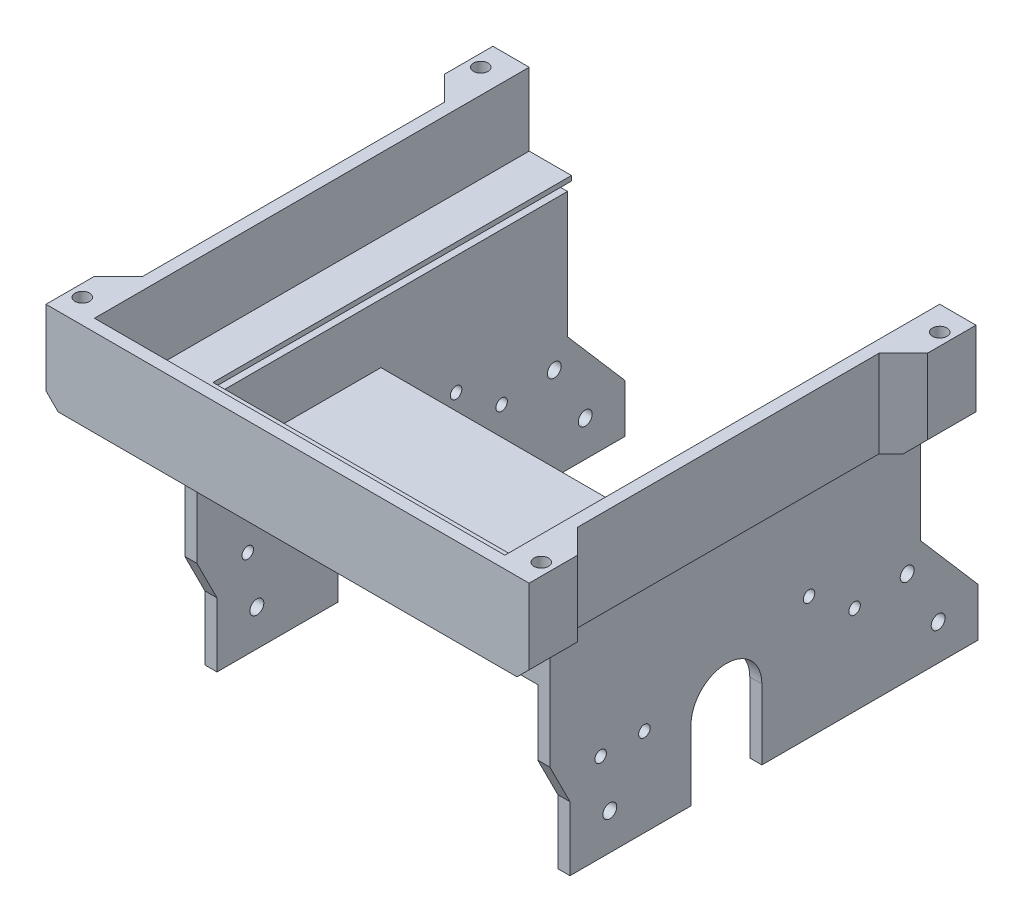
SolidWorks part; units mm, degrees
ref_plane "前视基准面" through (0, 0, 0) normal (0, 0, 1) x (1, 0, 0)
ref_plane "上视基准面" through (0, 0, 0) normal (0, 1, 0) x (1, 0, 0)
ref_plane "右视基准面" through (0, 0, 0) normal (1, 0, 0) x (0, 0, -1)
other "Configuration Table"
sketch "草图1" plane through (0, 0, 0) normal (1, 0, 0) x (0, 0, -1)
  line L0 (33.7, -13.6373) -> (33.7, -5.6373)
  line L1 (-33.7, -13.6373) -> (33.7, -13.6373)
  line L5 (24.2, -13.6373) -> (24.2, 5.3627)
  line L6 (33.7, -5.6373) -> (24.2, -5.6373)
  line L7 (24.2, 5.3627) -> (33.7, -5.6373)
  line L8 (24.2, 5.3627) -> (24.2, 10.3627)
  line L9 (24.2, 10.3627) -> (-37.02, 10.3627)
  line L10 (-33.7, -13.6373) -> (-33.7, -3.0373)
  line L11 (-37.02, 10.3627) -> (-37.02, 3.5627)
  line L12 (-37.02, 3.5627) -> (-33.7, -3.0373)
  line L13 (-33.7, -13.6373) -> (-13.7, -13.6373)
  line L14 (-13.7, -13.6373) -> (-2, -13.6373)
  line L16 (-2, -13.6373) -> (-13.7, -13.6373)
  line L17 (-2, -13.6373) -> (-2, -2.0373)
  line L18 (-2, -2.0373) -> (-13.7, -2.0373)
  line L19 (-13.7, -13.6373) -> (-13.7, -2.0373)
  circle A0 centre (-7.85, -2.0373) radius 5.85
  point P0 (0, 0)
  dimension "D1" = 67.4
  dimension "D2" = 8
  dimension "D3" = 19
  dimension "D4" = 9.5
  dimension "D5" = 5
  dimension "D6" = 61.22
  dimension "D7" = 10.6
  dimension "D8" = 6.8
  dimension "D9" = 20
  dimension "D10" = 11.7
  dimension "D11" = 11.6
extrude "凸台-拉伸1" add sketch "草图1" along normal blind 2 contours A0 L17 L1 L5 L8 L9 L11 L12 L10 L19 | L7 L5 L6 | L0 L6 L5 L1 region at (0, -9.6373, -28.95) region at (0, -1.9707, -27.3667) region at (0, -12.9798, -11.1)
sketch "草图2" plane through (2, 0, 0) normal (1, 0, 0) x (0, 0, -1)
  line L0 (28.27, -7.7273) -> (33.7, -7.7273)
  line L1 (27.12, -8.8773) -> (27.12, -13.6373)
  line L2 (-27.12, -8.7773) -> (-27.12, -13.6373)
  line L3 (-28.27, -7.6273) -> (-33.7, -7.6273)
  line L4 (24.2, 5.3627) -> (24.2, -13.6373)
  line L5 (33.7, 1.7127) -> (23.15, 1.7127)
  line L6 (22, 0.5627) -> (22, -13.6373)
  line L7 (33.7, -5.6373) -> (33.7, 10.3627)
  line L8 (33.7, 10.3627) -> (24.2, 10.3627)
  line L9 (14.26, 1.1127) -> (33.7, 1.1127)
  line L10 (13.31, 0.1627) -> (13.31, -13.6373)
  line L11 (-2, -2.0373) -> (-2, -13.6373)
  line L12 (-2, -13.6373) -> (33.7, -13.6373)
  line L13 (33.7, -13.6373) -> (33.7, -5.6373)
  line L14 (33.7, -5.6373) -> (24.2, 5.3627)
  line L15 (24.2, 5.3627) -> (24.2, 10.3627)
  line L16 (24.2, 10.3627) -> (-37.02, 10.3627)
  line L17 (-37.02, 10.3627) -> (-37.02, 3.5627)
  line L18 (-37.02, 3.5627) -> (-33.7, -3.0373)
  line L19 (-33.7, -3.0373) -> (-33.7, -13.6373)
  line L20 (-33.7, -13.6373) -> (-13.7, -13.6373)
  line L21 (-13.7, -13.6373) -> (-13.7, -2.0373)
  line L22 (-2, -2.0373) -> (-2, -13.6373)
  line L23 (-2, -13.6373) -> (33.7, -13.6373)
  line L24 (33.7, -13.6373) -> (33.7, -5.6373)
  line L25 (33.7, -5.6373) -> (24.2, 5.3627)
  line L26 (24.2, 5.3627) -> (24.2, 10.3627)
  line L27 (24.2, 10.3627) -> (-37.02, 10.3627)
  line L28 (-37.02, 10.3627) -> (-37.02, 3.5627)
  line L29 (-37.02, 3.5627) -> (-33.7, -3.0373)
  line L30 (-33.7, -3.0373) -> (-33.7, -13.6373)
  line L31 (-33.7, -13.6373) -> (-13.7, -13.6373)
  line L32 (-13.7, -13.6373) -> (-13.7, -2.0373)
  line L33 (6.74, 6.5927) -> (24.2, 6.5927)
  line L34 (5.79, 5.6427) -> (5.79, -13.6373)
  line L35 (-37.02, 3.5627) -> (-37.02, -13.6373)
  line L36 (-37.02, -13.6373) -> (-33.7, -13.6373)
  line L37 (-22.36, 0.9127) -> (-37.02, 0.9127)
  line L38 (-21.41, -0.0373) -> (-21.41, -13.6373)
  line L39 (-29.58, 0.9127) -> (-37.02, 0.9127)
  circle A0 centre (27.12, -7.7273) radius 1.15
  arc A1 (-2, -2.0373) -> (-13.7, -2.0373) centre (-7.85, -2.0373) ccw
  arc A2 (-2, -2.0373) -> (-13.7, -2.0373) centre (-7.85, -2.0373) ccw
  circle A3 centre (-27.12, -7.6273) radius 1.15
  circle A6 centre (22, 1.7127) radius 1.15
  circle A7 centre (13.31, 1.1127) radius 0.95
  circle A8 centre (5.79, 6.5927) radius 0.95
  circle A9 centre (-21.41, 0.9127) radius 0.95
  circle A10 centre (-28.63, 0.9127) radius 0.95
  dimension "D2" = 2.3
  dimension "D6" = 2.3
  dimension "D8" = 10.55
  dimension "D11" = 1.9
  dimension "D9" = 2.3
  dimension "D14" = 1.9
  dimension "D17" = 1.9
  dimension "D20" = 1.9
  dimension "D3" = 4.76
  dimension "D4" = 5.43
  dimension "D5" = 4.86
  dimension "D7" = 5.43
  dimension "D10" = 14.2
  dimension "D12" = 19.44
  dimension "D13" = 13.8
  dimension "D15" = 19.28
  dimension "D16" = 17.46
  dimension "D18" = 14.66
  dimension "D19" = 13.6
  dimension "D21" = 7.44
  dimension "D1" = 0
extrude "切除-拉伸1" cut sketch "草图2" against normal through all contours L37 A10 | L37 A10 | A9 | A3 | A8 | A7 | A6 L9 | L9 A6 | A0 L23 region at (2, -7.7273, -27.12) region at (2, 0.8874, -22) region at (2, 1.8983, -22) region at (2, 1.1127, -13.31) region at (2, 6.5927, -5.79) region at (2, 1.3159, 28.63) region at (2, 0.5095, 28.63) region at (2, -7.6273, 27.12) region at (2, 0.9127, 21.41)
sketch "草图3" plane through (0, 10.3627, 0) normal (0, 1, 0) x (1, 0, 0)
  line L4 (0, 24.2) -> (0, -37.02)
  line L5 (0, -37.02) -> (2, -37.02)
  line L6 (2, -37.02) -> (2, 24.2)
  line L7 (2, 24.2) -> (0, 24.2)
  line L8 (0, 24.2) -> (0, -37.02)
  line L9 (0, -37.02) -> (2, -37.02)
  line L10 (2, -37.02) -> (2, 24.2)
  line L11 (2, 24.2) -> (0, 24.2)
  dimension "D1" = 0
extrude "凸台-拉伸2" add sketch "草图3" along normal blind 6
sketch "草图4" plane through (0, 0, 0) normal (-1, 0, 0) x (0, 0, 1)
  line L1 (-24.2, 16.3627) -> (37.02, 16.3627)
  line L2 (-24.2, 16.3627) -> (-24.2, 14.3627)
  line L3 (-24.2, 14.3627) -> (37.02, 14.3627)
  line L4 (37.02, 16.3627) -> (37.02, 14.3627)
  line L11 (13.7, -2.0373) -> (13.7, -13.6373)
  line L12 (13.7, -13.6373) -> (33.7, -13.6373)
  line L13 (33.7, -13.6373) -> (33.7, -3.0373)
  line L14 (33.7, -3.0373) -> (37.02, 3.5627)
  line L15 (37.02, 3.5627) -> (37.02, 16.3627)
  line L16 (37.02, 16.3627) -> (-24.2, 16.3627)
  line L17 (-24.2, 16.3627) -> (-24.2, 5.3627)
  line L18 (-24.2, 5.3627) -> (-33.7, -5.6373)
  line L19 (-33.7, -5.6373) -> (-33.7, -13.6373)
  line L20 (-33.7, -13.6373) -> (2, -13.6373)
  line L21 (2, -13.6373) -> (2, -2.0373)
  line L22 (13.7, -2.0373) -> (13.7, -13.6373)
  line L23 (13.7, -13.6373) -> (33.7, -13.6373)
  line L24 (33.7, -13.6373) -> (33.7, -3.0373)
  line L25 (33.7, -3.0373) -> (37.02, 3.5627)
  line L26 (37.02, 3.5627) -> (37.02, 16.3627)
  line L27 (37.02, 16.3627) -> (-24.2, 16.3627)
  line L28 (-24.2, 16.3627) -> (-24.2, 5.3627)
  line L29 (-24.2, 5.3627) -> (-33.7, -5.6373)
  line L30 (-33.7, -5.6373) -> (-33.7, -13.6373)
  line L31 (-33.7, -13.6373) -> (2, -13.6373)
  line L32 (2, -13.6373) -> (2, -2.0373)
  arc A1 (13.7, -2.0373) -> (2, -2.0373) centre (7.85, -2.0373) ccw
  arc A2 (13.7, -2.0373) -> (2, -2.0373) centre (7.85, -2.0373) ccw
  line M25 (37.02, 3.5627) -> (37.02, 16.3627)
  line M26 (37.02, 16.3627) -> (-24.2, 16.3627)
  line M27 (-24.2, 16.3627) -> (-24.2, 5.3627)
  dimension "D2" = 2
  dimension "D1" = 0
extrude "凸台-拉伸3" add sketch "草图4" along normal blind 58.3 contours L3 M27 M25 M26 region at (0, 15.3627, 6.41)
sketch "草图5" plane through (-58.3, 0, 0) normal (-1, 0, 0) x (0, 0, 1)
  line L11 (37.02, 14.3627) -> (-24.2, 14.3627)
  line L12 (-24.2, 14.3627) -> (-24.2, 5.3627)
  line L13 (-24.2, 5.3627) -> (-33.7, -5.6373)
  line L14 (-33.7, -5.6373) -> (-33.7, -13.6373)
  line L15 (-33.7, -13.6373) -> (2, -13.6373)
  line L16 (2, -13.6373) -> (2, -2.0373)
  line L17 (13.7, -2.0373) -> (13.7, -13.6373)
  line L18 (13.7, -13.6373) -> (33.7, -13.6373)
  line L19 (33.7, -13.6373) -> (33.7, -3.0373)
  line L20 (33.7, -3.0373) -> (37.02, 3.5627)
  line L21 (37.02, 3.5627) -> (37.02, 14.3627)
  line L22 (37.02, 14.3627) -> (-24.2, 14.3627)
  line L23 (-24.2, 14.3627) -> (-24.2, 5.3627)
  line L24 (-24.2, 5.3627) -> (-33.7, -5.6373)
  line L25 (-33.7, -5.6373) -> (-33.7, -13.6373)
  line L26 (-33.7, -13.6373) -> (2, -13.6373)
  line L27 (2, -13.6373) -> (2, -2.0373)
  line L28 (13.7, -2.0373) -> (13.7, -13.6373)
  line L29 (13.7, -13.6373) -> (33.7, -13.6373)
  line L30 (33.7, -13.6373) -> (33.7, -3.0373)
  line L31 (33.7, -3.0373) -> (37.02, 3.5627)
  line L32 (37.02, 3.5627) -> (37.02, 14.3627)
  circle A0 centre (-13.31, 1.1127) radius 0.95 construction
  arc A1 (13.7, -2.0373) -> (2, -2.0373) centre (7.85, -2.0373) ccw
  arc A2 (13.7, -2.0373) -> (2, -2.0373) centre (7.85, -2.0373) ccw
  circle A3 centre (-13.31, 1.1127) radius 0.95
  circle A4 centre (-22, 1.7127) radius 1.15 construction
  circle A5 centre (-22, 1.7127) radius 1.15
  circle A6 centre (-27.12, -7.7273) radius 1.15 construction
  circle A7 centre (-27.12, -7.7273) radius 1.15
  circle A8 centre (-5.79, 6.5927) radius 0.95 construction
  circle A9 centre (-5.79, 6.5927) radius 0.95
  circle A10 centre (21.41, 0.9127) radius 0.95 construction
  circle A11 centre (21.41, 0.9127) radius 0.95
  circle A12 centre (28.63, 0.9127) radius 0.95 construction
  circle A13 centre (28.63, 0.9127) radius 0.95
  circle A14 centre (27.12, -7.6273) radius 1.15 construction
  circle A15 centre (27.12, -7.6273) radius 1.15
  dimension "D1" = 0
extrude "凸台-拉伸4" add sketch "草图5" against normal blind 2
sketch "草图7" plane through (0, 0, 37.02) normal (0, 0, 1) x (1, 0, 0)
  line L0 (-28.15, 14.3627) -> (-28.15, 8.4109) construction
  line L1 (-58.3, 16.3627) -> (-56.3, 16.3627)
  line L2 (-58.3, 16.3627) -> (-58.3, 26.3627)
  line L3 (-58.3, 26.3627) -> (-56.3, 26.3627)
  line L4 (-56.3, 16.3627) -> (-56.3, 26.3627)
  line L5 (-56.3, 26.3627) -> (0, 26.3627)
  line L6 (2, 16.3627) -> (0, 16.3627)
  line L7 (2, 16.3627) -> (2, 26.3627)
  line L8 (2, 16.3627) -> (-58.3, 16.3627)
  line L9 (-58.3, 16.3627) -> (-58.3, 3.5627)
  line L10 (-58.3, 3.5627) -> (-56.3, 3.5627)
  line L11 (-56.3, 3.5627) -> (-56.3, 14.3627)
  line L12 (-56.3, 14.3627) -> (0, 14.3627)
  line L13 (0, 14.3627) -> (0, 3.5627)
  line L14 (0, 3.5627) -> (2, 3.5627)
  line L15 (2, 3.5627) -> (2, 16.3627)
  line L16 (2, 16.3627) -> (-58.3, 16.3627)
  line L17 (-58.3, 16.3627) -> (-58.3, 3.5627)
  line L18 (-58.3, 3.5627) -> (-56.3, 3.5627)
  line L19 (-56.3, 3.5627) -> (-56.3, 14.3627)
  line L20 (-56.3, 14.3627) -> (0, 14.3627)
  line L21 (0, 14.3627) -> (0, 3.5627)
  line L22 (0, 3.5627) -> (2, 3.5627)
  line L23 (2, 3.5627) -> (2, 16.3627)
  line L24 (2, 26.3627) -> (0, 26.3627)
  line L25 (0, 16.3627) -> (0, 26.3627)
  line L26 (-58.15, 26.3627) -> (1.85, 26.3627)
  line L27 (-58.15, 28.7627) -> (-55.65, 28.7627)
  line L28 (-58.15, 26.3627) -> (1.85, 26.3627)
  line L29 (-58.15, 26.3627) -> (-58.15, 27.9627)
  line L30 (-58.15, 27.9627) -> (1.85, 27.9627)
  line L31 (1.85, 26.3627) -> (1.85, 27.9627)
  line L32 (-58.15, 28.7627) -> (-55.65, 28.7627)
  line L33 (-55.65, 28.7627) -> (-55.65, 27.9627)
  line L34 (-60.15, 26.3627) -> (-58.3, 21.3627)
  line L35 (-58.15, 28.7627) -> (-60.15, 28.7627)
  line L36 (-58.15, 28.7627) -> (-58.15, 26.3627)
  line L37 (-58.15, 26.3627) -> (-60.15, 26.3627)
  line L38 (-60.15, 28.7627) -> (-60.15, 26.3627)
  line L39 (-58.15, 28.7627) -> (1.85, 28.7627) construction
  line L40 (3.85, 26.3627) -> (2, 21.3627)
  line L41 (-0.65, 28.7627) -> (-0.65, 27.9627)
  line L42 (1.85, 26.3627) -> (3.85, 26.3627)
  line L43 (3.85, 28.7627) -> (3.85, 26.3627)
  line L44 (1.85, 28.7627) -> (3.85, 28.7627)
  line L45 (1.85, 28.7627) -> (1.85, 26.3627)
  line L46 (1.85, 28.7627) -> (-0.65, 28.7627)
  point P19 (-28.15, 26.3627)
  dimension "D2" = 10
  dimension "D3" = 60
  dimension "D4" = 1.6
  dimension "D6" = 2.5
  dimension "D7" = 2
  dimension "D1" = 0
  dimension "D5" = 0.8
extrude "凸台-拉伸5" add sketch "草图7" against normal up to surface (61.22 mm away) contours L35 L38 L37 L3 L29 L36 | L27 L36 L30 L33 | L2 L37 L34 | L45 L46 L41 L30 | L44 L45 L31 L24 L42 L43 | L42 L7 L40 | L2 L1 L4 L3 | L7 L6 L25 L24 region at (-58.9167, 24.696, 37.02) region at (-59.15, 27.5627, 37.02) region at (-56.9, 28.3627, 37.02) region at (2.85, 27.5627, 37.02) region at (2.6167, 24.696, 37.02) region at (0.6, 28.3627, 37.02) up to face at (-28.15, 10.3627, -24.2)
sketch "草图8" plane through (0, 0, 37.02) normal (0, 0, 1) x (1, 0, 0)
  line L0 (-55.65, 28.7627) -> (-0.65, 28.7627)
  line L24 (0, 16.3627) -> (-56.3, 16.3627)
  line L25 (-56.3, 16.3627) -> (-56.3, 26.3627)
  line L26 (-56.3, 26.3627) -> (-58.15, 26.3627)
  line L27 (-58.15, 26.3627) -> (-58.15, 27.9627)
  line L28 (-58.15, 27.9627) -> (-55.65, 27.9627)
  line L29 (-55.65, 27.9627) -> (-55.65, 28.7627)
  line L30 (-55.65, 28.7627) -> (-60.15, 28.7627)
  line L31 (-60.15, 28.7627) -> (-60.15, 26.3627)
  line L32 (-60.15, 26.3627) -> (-58.3, 21.3627)
  line L33 (-58.3, 21.3627) -> (-58.3, 3.5627)
  line L34 (-58.3, 3.5627) -> (-56.3, 3.5627)
  line L35 (-56.3, 3.5627) -> (-56.3, 14.3627)
  line L36 (-56.3, 14.3627) -> (0, 14.3627)
  line L37 (0, 14.3627) -> (0, 3.5627)
  line L38 (0, 3.5627) -> (2, 3.5627)
  line L39 (2, 3.5627) -> (2, 21.3627)
  line L40 (2, 21.3627) -> (3.85, 26.3627)
  line L41 (3.85, 26.3627) -> (3.85, 28.7627)
  line L42 (3.85, 28.7627) -> (-0.65, 28.7627)
  line L43 (-0.65, 28.7627) -> (-0.65, 27.9627)
  line L44 (-0.65, 27.9627) -> (1.85, 27.9627)
  line L45 (1.85, 27.9627) -> (1.85, 26.3627)
  line L46 (1.85, 26.3627) -> (0, 26.3627)
  line L47 (0, 26.3627) -> (0, 16.3627)
  line L48 (0, 16.3627) -> (-56.3, 16.3627)
  line L49 (-56.3, 16.3627) -> (-56.3, 26.3627)
  line L50 (-56.3, 26.3627) -> (-58.15, 26.3627)
  line L51 (-58.15, 26.3627) -> (-58.15, 27.9627)
  line L52 (-58.15, 27.9627) -> (-55.65, 27.9627)
  line L53 (-55.65, 27.9627) -> (-55.65, 28.7627)
  line L54 (-55.65, 28.7627) -> (-60.15, 28.7627)
  line L55 (-60.15, 28.7627) -> (-60.15, 26.3627)
  line L56 (-60.15, 26.3627) -> (-58.3, 21.3627)
  line L57 (-58.3, 21.3627) -> (-58.3, 3.5627)
  line L58 (-58.3, 3.5627) -> (-56.3, 3.5627)
  line L59 (-56.3, 3.5627) -> (-56.3, 14.3627)
  line L60 (-56.3, 14.3627) -> (0, 14.3627)
  line L61 (0, 14.3627) -> (0, 3.5627)
  line L62 (0, 3.5627) -> (2, 3.5627)
  line L63 (2, 3.5627) -> (2, 21.3627)
  line L64 (2, 21.3627) -> (3.85, 26.3627)
  line L65 (3.85, 26.3627) -> (3.85, 28.7627)
  line L66 (3.85, 28.7627) -> (-0.65, 28.7627)
  line L67 (-0.65, 28.7627) -> (-0.65, 27.9627)
  line L68 (-0.65, 27.9627) -> (1.85, 27.9627)
  line L69 (1.85, 27.9627) -> (1.85, 26.3627)
  line L70 (1.85, 26.3627) -> (0, 26.3627)
  line L71 (0, 26.3627) -> (0, 16.3627)
  line M25 (0, 16.3627) -> (-56.3, 16.3627)
  line M26 (-56.3, 16.3627) -> (-56.3, 26.3627)
  line M27 (-56.3, 26.3627) -> (-58.15, 26.3627)
  line M28 (-58.15, 26.3627) -> (-58.15, 27.9627)
  line M29 (-58.15, 27.9627) -> (-55.65, 27.9627)
  line M30 (-55.65, 27.9627) -> (-55.65, 28.7627)
  line M31 (-55.65, 28.7627) -> (-60.15, 28.7627)
  line M32 (-60.15, 28.7627) -> (-60.15, 26.3627)
  line M33 (-60.15, 26.3627) -> (-58.3, 21.3627)
  line M34 (-58.3, 21.3627) -> (-58.3, 3.5627)
  line M35 (-58.3, 3.5627) -> (-56.3, 3.5627)
  line M36 (-56.3, 3.5627) -> (-56.3, 14.3627)
  line M37 (-56.3, 14.3627) -> (0, 14.3627)
  line M38 (0, 14.3627) -> (0, 3.5627)
  line M39 (0, 3.5627) -> (2, 3.5627)
  line M40 (2, 3.5627) -> (2, 21.3627)
  line M41 (2, 21.3627) -> (3.85, 26.3627)
  line M42 (3.85, 26.3627) -> (3.85, 28.7627)
  line M43 (3.85, 28.7627) -> (-0.65, 28.7627)
  line M44 (-0.65, 28.7627) -> (-0.65, 27.9627)
  line M45 (-0.65, 27.9627) -> (1.85, 27.9627)
  line M46 (1.85, 27.9627) -> (1.85, 26.3627)
  line M47 (1.85, 26.3627) -> (0, 26.3627)
  line M48 (0, 26.3627) -> (0, 16.3627)
  dimension "D1" = 0
extrude "凸台-拉伸6" add sketch "草图8" against normal blind 2 contours L0 M30 M29 M28 M27 M26 M25 M48 M47 M46 M45 M44 | M48 M25 M26 M27 M28 M29 M30 M31 M32 M33 M34 M35 M36 M37 M38 M39 M40 M41 M42 M43 M44 M45 M46 M47 region at (-28.15, 22.5928, 37.02) region at (-28.15, 16.3288, 37.02)
sketch "草图10" plane through (0, 26.3627, 0) normal (0, 1, 0) x (1, 0, 0)
  line L4 (0, 24.2) -> (0, -35.02)
  line L5 (0, -35.02) -> (1.85, -35.02)
  line L6 (1.85, -35.02) -> (1.85, 24.2)
  line L7 (1.85, 24.2) -> (0, 24.2)
  line L8 (0, 24.2) -> (0, -35.02)
  line L9 (0, -35.02) -> (1.85, -35.02)
  line L10 (1.85, -35.02) -> (1.85, 24.2)
  line L11 (1.85, 24.2) -> (0, 24.2)
  line L12 (-58.15, -35.02) -> (-56.3, -35.02)
  line L13 (-56.3, -35.02) -> (-56.3, 24.2)
  line L14 (-56.3, 24.2) -> (-58.15, 24.2)
  line L15 (-58.15, 24.2) -> (-58.15, -35.02)
  line L16 (-58.15, -35.02) -> (-56.3, -35.02)
  line L17 (-56.3, -35.02) -> (-56.3, 24.2)
  line L18 (-56.3, 24.2) -> (-58.15, 24.2)
  line L19 (-58.15, 24.2) -> (-58.15, -35.02)
  dimension "D1" = 0
  dimension "D2" = 0
extrude "切除-拉伸2" cut sketch "草图10" against normal blind 0.2
sketch "草图11" plane through (0, 0, -24.2) normal (0, 0, -1) x (-1, 0, 0)
  line L1 (-1.85, 26.1627) -> (-1.97, 26.1627)
  line L2 (-1.85, 26.1627) -> (-1.85, 27.9627)
  line L3 (-1.85, 27.9627) -> (-1.97, 27.9627)
  line L4 (-1.97, 26.1627) -> (-1.97, 27.9627)
  line L5 (58.15, 27.9627) -> (58.27, 27.9627)
  line L6 (58.15, 27.9627) -> (58.15, 26.1627)
  line L7 (58.15, 26.1627) -> (58.27, 26.1627)
  line L8 (58.27, 27.9627) -> (58.27, 26.1627)
  line L24 (0, 26.1627) -> (-1.85, 26.1627)
  line L25 (-1.85, 26.1627) -> (-1.85, 27.9627)
  line L26 (-1.85, 27.9627) -> (0.65, 27.9627)
  line L27 (0.65, 27.9627) -> (0.65, 28.7627)
  line L28 (0.65, 28.7627) -> (-3.85, 28.7627)
  line L29 (-3.85, 28.7627) -> (-3.85, 26.3627)
  line L30 (-3.85, 26.3627) -> (-2, 21.3627)
  line L31 (-2, 21.3627) -> (-2, 5.3627)
  line L32 (-2, 5.3627) -> (0, 5.3627)
  line L33 (0, 5.3627) -> (0, 14.3627)
  line L34 (0, 14.3627) -> (56.3, 14.3627)
  line L35 (56.3, 14.3627) -> (56.3, 5.3627)
  line L36 (56.3, 5.3627) -> (58.3, 5.3627)
  line L37 (58.3, 5.3627) -> (58.3, 21.3627)
  line L38 (58.3, 21.3627) -> (60.15, 26.3627)
  line L39 (60.15, 26.3627) -> (60.15, 28.7627)
  line L40 (60.15, 28.7627) -> (55.65, 28.7627)
  line L41 (55.65, 28.7627) -> (55.65, 27.9627)
  line L42 (55.65, 27.9627) -> (58.15, 27.9627)
  line L43 (58.15, 27.9627) -> (58.15, 26.1627)
  line L44 (58.15, 26.1627) -> (56.3, 26.1627)
  line L45 (56.3, 26.1627) -> (56.3, 16.3627)
  line L46 (56.3, 16.3627) -> (0, 16.3627)
  line L47 (0, 16.3627) -> (0, 26.1627)
  line L48 (0, 26.1627) -> (-1.85, 26.1627)
  line L49 (-1.85, 26.1627) -> (-1.85, 27.9627)
  line L50 (-1.85, 27.9627) -> (0.65, 27.9627)
  line L51 (0.65, 27.9627) -> (0.65, 28.7627)
  line L52 (0.65, 28.7627) -> (-3.85, 28.7627)
  line L53 (-3.85, 28.7627) -> (-3.85, 26.3627)
  line L54 (-3.85, 26.3627) -> (-2, 21.3627)
  line L55 (-2, 21.3627) -> (-2, 5.3627)
  line L56 (-2, 5.3627) -> (0, 5.3627)
  line L57 (0, 5.3627) -> (0, 14.3627)
  line L58 (0, 14.3627) -> (56.3, 14.3627)
  line L59 (56.3, 14.3627) -> (56.3, 5.3627)
  line L60 (56.3, 5.3627) -> (58.3, 5.3627)
  line L61 (58.3, 5.3627) -> (58.3, 21.3627)
  line L62 (58.3, 21.3627) -> (60.15, 26.3627)
  line L63 (60.15, 26.3627) -> (60.15, 28.7627)
  line L64 (60.15, 28.7627) -> (55.65, 28.7627)
  line L65 (55.65, 28.7627) -> (55.65, 27.9627)
  line L66 (55.65, 27.9627) -> (58.15, 27.9627)
  line L67 (58.15, 27.9627) -> (58.15, 26.1627)
  line L68 (58.15, 26.1627) -> (56.3, 26.1627)
  line L69 (56.3, 26.1627) -> (56.3, 16.3627)
  line L70 (56.3, 16.3627) -> (0, 16.3627)
  line L71 (0, 16.3627) -> (0, 26.1627)
  line M28 (-1.85, 26.1627) -> (-1.85, 27.9627)
  line M46 (58.15, 27.9627) -> (58.15, 26.1627)
  dimension "D2" = 0.12
  dimension "D3" = 0.12
  dimension "D1" = 0
extrude "切除-拉伸4" cut sketch "草图11" against normal up to surface (59.22 mm away) contours L4 L1 L3 M28 | L8 L5 L7 M46 region at (1.91, 27.0627, -24.2) region at (-58.21, 27.0627, -24.2) up to face at (-28.15, 25.5627, 35.02)
sketch "草图12" plane through (0, 0, -24.2) normal (0, 0, -1) x (-1, 0, 0)
  line L1 (0, 16.3627) -> (56.3, 16.3627)
  line L2 (0, 16.3627) -> (0, 14.3627)
  line L3 (0, 14.3627) -> (56.3, 14.3627)
  line L4 (56.3, 16.3627) -> (56.3, 14.3627)
  line L24 (-1.97, 26.1627) -> (-1.97, 27.9627)
  line L25 (-1.97, 27.9627) -> (0.65, 27.9627)
  line L26 (0.65, 27.9627) -> (0.65, 28.7627)
  line L27 (0.65, 28.7627) -> (-3.85, 28.7627)
  line L28 (-3.85, 28.7627) -> (-3.85, 26.3627)
  line L29 (-3.85, 26.3627) -> (-2, 21.3627)
  line L30 (-2, 21.3627) -> (-2, 5.3627)
  line L31 (-2, 5.3627) -> (0, 5.3627)
  line L32 (0, 5.3627) -> (0, 14.3627)
  line L33 (0, 14.3627) -> (56.3, 14.3627)
  line L34 (56.3, 14.3627) -> (56.3, 5.3627)
  line L35 (56.3, 5.3627) -> (58.3, 5.3627)
  line L36 (58.3, 5.3627) -> (58.3, 21.3627)
  line L37 (58.3, 21.3627) -> (60.15, 26.3627)
  line L38 (60.15, 26.3627) -> (60.15, 28.7627)
  line L39 (60.15, 28.7627) -> (55.65, 28.7627)
  line L40 (55.65, 28.7627) -> (55.65, 27.9627)
  line L41 (55.65, 27.9627) -> (58.27, 27.9627)
  line L42 (58.27, 27.9627) -> (58.27, 26.1627)
  line L43 (58.27, 26.1627) -> (56.3, 26.1627)
  line L44 (56.3, 26.1627) -> (56.3, 16.3627)
  line L45 (56.3, 16.3627) -> (0, 16.3627)
  line L46 (0, 16.3627) -> (0, 26.1627)
  line L47 (0, 26.1627) -> (-1.97, 26.1627)
  line L48 (-1.97, 26.1627) -> (-1.97, 27.9627)
  line L49 (-1.97, 27.9627) -> (0.65, 27.9627)
  line L50 (0.65, 27.9627) -> (0.65, 28.7627)
  line L51 (0.65, 28.7627) -> (-3.85, 28.7627)
  line L52 (-3.85, 28.7627) -> (-3.85, 26.3627)
  line L53 (-3.85, 26.3627) -> (-2, 21.3627)
  line L54 (-2, 21.3627) -> (-2, 5.3627)
  line L55 (-2, 5.3627) -> (0, 5.3627)
  line L56 (0, 5.3627) -> (0, 14.3627)
  line L57 (0, 14.3627) -> (56.3, 14.3627)
  line L58 (56.3, 14.3627) -> (56.3, 5.3627)
  line L59 (56.3, 5.3627) -> (58.3, 5.3627)
  line L60 (58.3, 5.3627) -> (58.3, 21.3627)
  line L61 (58.3, 21.3627) -> (60.15, 26.3627)
  line L62 (60.15, 26.3627) -> (60.15, 28.7627)
  line L63 (60.15, 28.7627) -> (55.65, 28.7627)
  line L64 (55.65, 28.7627) -> (55.65, 27.9627)
  line L65 (55.65, 27.9627) -> (58.27, 27.9627)
  line L66 (58.27, 27.9627) -> (58.27, 26.1627)
  line L67 (58.27, 26.1627) -> (56.3, 26.1627)
  line L68 (56.3, 26.1627) -> (56.3, 16.3627)
  line L69 (56.3, 16.3627) -> (0, 16.3627)
  line L70 (0, 16.3627) -> (0, 26.1627)
  line L71 (0, 26.1627) -> (-1.97, 26.1627)
  line M38 (0, 14.3627) -> (56.3, 14.3627)
  line M50 (56.3, 16.3627) -> (0, 16.3627)
  dimension "D1" = 0
extrude "切除-拉伸5" cut sketch "草图12" against normal up to surface (30.82 mm away) contours L4 L2 M50 M38 region at (-28.15, 15.3627, -24.2)
sketch "草图13" plane through (0, 0, 37.02) normal (0, 0, 1) x (1, 0, 0)
  line L0 (-58.3, 21.3627) -> (2, 21.3627)
  line L12 (3.85, 26.3627) -> (3.85, 28.7627)
  line L13 (3.85, 28.7627) -> (-60.15, 28.7627)
  line L14 (-60.15, 28.7627) -> (-60.15, 26.3627)
  line L15 (-60.15, 26.3627) -> (-58.3, 21.3627)
  line L16 (-58.3, 21.3627) -> (-58.3, 3.5627)
  line L17 (-58.3, 3.5627) -> (-56.3, 3.5627)
  line L18 (-56.3, 3.5627) -> (-56.3, 14.3627)
  line L19 (-56.3, 14.3627) -> (0, 14.3627)
  line L20 (0, 14.3627) -> (0, 3.5627)
  line L21 (0, 3.5627) -> (2, 3.5627)
  line L22 (2, 3.5627) -> (2, 21.3627)
  line L23 (2, 21.3627) -> (3.85, 26.3627)
  line L24 (3.85, 26.3627) -> (3.85, 28.7627)
  line L25 (3.85, 28.7627) -> (-60.15, 28.7627)
  line L26 (-60.15, 28.7627) -> (-60.15, 26.3627)
  line L27 (-60.15, 26.3627) -> (-58.3, 21.3627)
  line L28 (-58.3, 21.3627) -> (-58.3, 3.5627)
  line L29 (-58.3, 3.5627) -> (-56.3, 3.5627)
  line L30 (-56.3, 3.5627) -> (-56.3, 14.3627)
  line L31 (-56.3, 14.3627) -> (0, 14.3627)
  line L32 (0, 14.3627) -> (0, 3.5627)
  line L33 (0, 3.5627) -> (2, 3.5627)
  line L34 (2, 3.5627) -> (2, 21.3627)
  line L35 (2, 21.3627) -> (3.85, 26.3627)
  line M14 (3.85, 26.3627) -> (3.85, 28.7627)
  line M15 (3.85, 28.7627) -> (-60.15, 28.7627)
  line M16 (-60.15, 28.7627) -> (-60.15, 26.3627)
  line M17 (-60.15, 26.3627) -> (-58.3, 21.3627)
  line M25 (2, 21.3627) -> (3.85, 26.3627)
  dimension "D1" = 0
extrude "凸台-拉伸7" add sketch "草图13" along normal up to surface (10.6 mm away) contours L0 M17 M25 M14 M15 M16 region at (-28.15, 25.1032, 37.02)
sketch "草图14" plane through (3.85, 0, 0) normal (1, 0, 0) x (0, 0, -1)
  line L4 (24.2, 28.7627) -> (-47.62, 28.7627)
  line L5 (-47.62, 28.7627) -> (-47.62, 26.3627)
  line L6 (-47.62, 26.3627) -> (24.2, 26.3627)
  line L7 (24.2, 26.3627) -> (24.2, 28.7627)
  line L8 (24.2, 28.7627) -> (-47.62, 28.7627)
  line L9 (-47.62, 28.7627) -> (-47.62, 26.3627)
  line L10 (-47.62, 26.3627) -> (24.2, 26.3627)
  line L11 (24.2, 26.3627) -> (24.2, 28.7627)
  dimension "D1" = 0
extrude "凸台-拉伸8" add sketch "草图14" along normal up to surface (1.32 mm away)
sketch "草图15" plane through (-60.15, 0, 0) normal (-1, 0, 0) x (0, 0, 1)
  line L4 (-24.2, 26.3627) -> (47.62, 26.3627)
  line L5 (47.62, 26.3627) -> (47.62, 28.7627)
  line L6 (47.62, 28.7627) -> (-24.2, 28.7627)
  line L7 (-24.2, 28.7627) -> (-24.2, 26.3627)
  line L8 (-24.2, 26.3627) -> (47.62, 26.3627)
  line L9 (47.62, 26.3627) -> (47.62, 28.7627)
  line L10 (47.62, 28.7627) -> (-24.2, 28.7627)
  line L11 (-24.2, 28.7627) -> (-24.2, 26.3627)
  dimension "D1" = 0
extrude "凸台-拉伸9" add sketch "草图15" along normal up to surface (2.48 mm away) up to face at (1, -13.6373, -15.85)
sketch "草图16" plane through (0, 0, 47.62) normal (0, 0, 1) x (1, 0, 0)
  line L8 (-58.3, 21.3627) -> (2, 21.3627)
  line L9 (2, 21.3627) -> (3.85, 26.3627)
  line L10 (3.85, 26.3627) -> (5.17, 26.3627)
  line L11 (5.17, 26.3627) -> (5.17, 28.7627)
  line L12 (5.17, 28.7627) -> (-62.63, 28.7627)
  line L13 (-62.63, 28.7627) -> (-62.63, 26.3627)
  line L14 (-62.63, 26.3627) -> (-60.15, 26.3627)
  line L15 (-60.15, 26.3627) -> (-58.3, 21.3627)
  line L16 (-58.3, 21.3627) -> (2, 21.3627)
  line L17 (2, 21.3627) -> (3.85, 26.3627)
  line L18 (3.85, 26.3627) -> (5.17, 26.3627)
  line L19 (5.17, 26.3627) -> (5.17, 28.7627)
  line L20 (5.17, 28.7627) -> (-62.63, 28.7627)
  line L21 (-62.63, 28.7627) -> (-62.63, 26.3627)
  line L22 (-62.63, 26.3627) -> (-60.15, 26.3627)
  line L23 (-60.15, 26.3627) -> (-58.3, 21.3627)
  dimension "D1" = 0
extrude "凸台-拉伸10" add sketch "草图16" along normal blind 2
sketch "草图17" plane through (5.17, 0, 0) normal (1, 0, 0) x (0, 0, -1)
  line L4 (24.2, 28.7627) -> (-49.62, 28.7627)
  line L5 (-49.62, 28.7627) -> (-49.62, 26.3627)
  line L6 (-49.62, 26.3627) -> (24.2, 26.3627)
  line L7 (24.2, 26.3627) -> (24.2, 28.7627)
  line L8 (24.2, 28.7627) -> (-49.62, 28.7627)
  line L9 (-49.62, 28.7627) -> (-49.62, 26.3627)
  line L10 (-49.62, 26.3627) -> (24.2, 26.3627)
  line L11 (24.2, 26.3627) -> (24.2, 28.7627)
  dimension "D1" = 0
extrude "凸台-拉伸11" add sketch "草图17" along normal blind 2
sketch "草图18" plane through (-62.63, 0, 0) normal (-1, 0, 0) x (0, 0, 1)
  line L4 (49.62, 28.7627) -> (-24.2, 28.7627)
  line L5 (-24.2, 28.7627) -> (-24.2, 26.3627)
  line L6 (-24.2, 26.3627) -> (49.62, 26.3627)
  line L7 (49.62, 26.3627) -> (49.62, 28.7627)
  line L8 (49.62, 28.7627) -> (-24.2, 28.7627)
  line L9 (-24.2, 28.7627) -> (-24.2, 26.3627)
  line L10 (-24.2, 26.3627) -> (49.62, 26.3627)
  line L11 (49.62, 26.3627) -> (49.62, 28.7627)
  dimension "D1" = 0
extrude "凸台-拉伸12" add sketch "草图18" along normal blind 2
sketch "草图19" plane through (0, 28.7627, 0) normal (0, 1, 0) x (1, 0, 0)
  line L0 (-62.63, 22.2) -> (-62.63, -47.62)
  line L1 (-62.63, -47.62) -> (5.17, -47.62)
  line L2 (5.17, -47.62) -> (5.17, 22.2)
  line L3 (5.17, 22.2) -> (1.35, 22.2)
  line L4 (1.35, 22.2) -> (1.35, -37.02)
  line L5 (1.35, -37.02) -> (-57.65, -37.02)
  line L6 (-57.65, -37.02) -> (-57.65, 22.2)
  line L7 (-57.65, 22.2) -> (-62.63, 22.2)
  line L8 (-55.65, 24.2) -> (-64.63, 24.2)
  line L9 (-64.63, 24.2) -> (-64.63, -49.62)
  line L10 (-64.63, -49.62) -> (7.17, -49.62)
  line L11 (7.17, -49.62) -> (7.17, 24.2)
  line L12 (7.17, 24.2) -> (-0.65, 24.2)
  line L13 (-0.65, 24.2) -> (-0.65, -35.02)
  line L14 (-0.65, -35.02) -> (-55.65, -35.02)
  line L15 (-55.65, -35.02) -> (-55.65, 24.2)
  line L16 (-55.65, 24.2) -> (-64.63, 24.2)
  line L17 (-64.63, 24.2) -> (-64.63, -49.62)
  line L18 (-64.63, -49.62) -> (7.17, -49.62)
  line L19 (7.17, -49.62) -> (7.17, 24.2)
  line L20 (7.17, 24.2) -> (-0.65, 24.2)
  line L21 (-0.65, 24.2) -> (-0.65, -35.02)
  line L22 (-0.65, -35.02) -> (-55.65, -35.02)
  line L23 (-55.65, -35.02) -> (-55.65, 24.2)
  line L24 (-62.63, 22.2) -> (-62.63, 24.2)
  line L25 (-62.63, 24.2) -> (1.35, 24.2)
  line L26 (1.35, 24.2) -> (1.35, 22.2)
  line L27 (5.17, 22.2) -> (5.17, 24.2)
  line M13 (-64.63, 24.2) -> (-64.63, -49.62)
  line M14 (-64.63, -49.62) -> (7.17, -49.62)
  line M15 (7.17, -49.62) -> (7.17, 24.2)
  line M16 (7.17, 24.2) -> (-0.65, 24.2)
  dimension "D1" = 0
  dimension "D2" = 2
extrude "凸台-拉伸13" add sketch "草图19" along normal blind 12 contours L27 L2 L1 L0 L24 L16 M13 M14 M15 M16 region at (-63.6598, 28.7627, 12.71)
sketch "草图20" plane through (0, 40.7627, 0) normal (0, 1, 0) x (1, 0, 0)
  line L0 (-28.73, -49.62) -> (-28.73, -39.7517)
  line L1 (-64.63, 24.2) -> (-68.63, 24.2)
  line L2 (-64.63, 24.2) -> (-64.63, 16.2)
  line L3 (-64.63, 16.2) -> (-68.63, 16.2)
  line L4 (-68.63, 24.2) -> (-68.63, 16.2)
  line L5 (-64.63, -49.62) -> (-68.63, -49.62)
  line L6 (-64.63, -49.62) -> (-64.63, -41.62)
  line L7 (-64.63, -41.62) -> (-68.63, -41.62)
  line L8 (5.17, 24.2) -> (5.17, -47.62)
  line L9 (5.17, -47.62) -> (-62.63, -47.62)
  line L10 (-62.63, -47.62) -> (-62.63, 24.2)
  line L11 (-62.63, 24.2) -> (-64.63, 24.2)
  line L12 (-64.63, 24.2) -> (-64.63, -49.62)
  line L13 (-64.63, -49.62) -> (7.17, -49.62)
  line L14 (7.17, -49.62) -> (7.17, 24.2)
  line L15 (7.17, 24.2) -> (5.17, 24.2)
  line L16 (5.17, 24.2) -> (5.17, -47.62)
  line L17 (5.17, -47.62) -> (-62.63, -47.62)
  line L18 (-62.63, -47.62) -> (-62.63, 24.2)
  line L19 (-62.63, 24.2) -> (-64.63, 24.2)
  line L20 (-64.63, 24.2) -> (-64.63, -49.62)
  line L21 (-64.63, -49.62) -> (7.17, -49.62)
  line L22 (7.17, -49.62) -> (7.17, 24.2)
  line L23 (7.17, 24.2) -> (5.17, 24.2)
  line L24 (-68.63, -49.62) -> (-68.63, -41.62)
  line L25 (7.17, -41.62) -> (11.17, -41.62)
  line L26 (11.17, -49.62) -> (11.17, -41.62)
  line L27 (7.17, -49.62) -> (11.17, -49.62)
  line L28 (7.17, -49.62) -> (7.17, -41.62)
  line L29 (7.17, 16.2) -> (11.17, 16.2)
  line L30 (11.17, 24.2) -> (11.17, 16.2)
  line L31 (7.17, 24.2) -> (11.17, 24.2)
  line L32 (7.17, 24.2) -> (7.17, 16.2)
  line L33 (-68.63, 24.2) -> (-64.63, 16.2)
  line L34 (-68.63, -41.62) -> (-64.63, -49.62)
  circle A0 centre (-66.63, 20.2) radius 1.2
  circle A1 centre (-66.63, -45.62) radius 1.2
  circle A2 centre (9.17, 20.2) radius 1.2
  circle A3 centre (9.17, -45.62) radius 1.2
  line M22 (-64.63, 24.2) -> (-64.63, -49.62)
  line M24 (7.17, -49.62) -> (7.17, 24.2)
  dimension "D5" = 2.4
  dimension "D6" = 2.4
  dimension "D2" = 4
  dimension "D3" = 8
  dimension "D4" = 8
  dimension "D1" = 0
extrude "凸台-拉伸14" add sketch "草图20" against normal blind 10 contours A0 L33 L1 M22 | A0 L33 L4 L3 | A1 L34 L7 M22 | A1 L34 L24 L5 | L27 L26 L25 A3 M24 | L31 L29 L30 A2 M24 region at (-65.9286, 40.7627, 44.1046) region at (-67.3314, 40.7627, 47.1354) region at (7.2594, 40.7627, 45.62) region at (-65.9286, 40.7627, -21.7154) region at (-67.3314, 40.7627, -18.6846) region at (7.2594, 40.7627, -20.2)
sketch "草图21" plane through (0, 30.7627, 0) normal (0, -1, 0) x (1, 0, 0)
  line L0 (-64.63, 49.62) -> (-68.63, 49.62) construction
  line L1 (-68.63, 49.62) -> (-68.63, 41.62) construction
  line L2 (-68.63, 41.62) -> (-64.63, 41.62) construction
  line L3 (-64.63, 41.62) -> (-64.63, 49.62) construction
  line L4 (-64.63, -16.2) -> (-68.63, -16.2)
  line L5 (-68.63, -16.2) -> (-68.63, -24.2)
  line L6 (-68.63, -24.2) -> (-64.63, -24.2)
  line L7 (-64.63, -24.2) -> (-64.63, -16.2)
  line L8 (-64.63, -16.2) -> (-68.63, -16.2)
  line L9 (-68.63, -16.2) -> (-68.63, -24.2)
  line L10 (-68.63, -24.2) -> (-64.63, -24.2)
  line L11 (-64.63, -24.2) -> (-64.63, -16.2)
  line L12 (7.17, -24.2) -> (11.17, -24.2) construction
  line L13 (11.17, -24.2) -> (11.17, -16.2) construction
  line L14 (11.17, -16.2) -> (7.17, -16.2) construction
  line L15 (7.17, -16.2) -> (7.17, -24.2) construction
  line L16 (7.17, 49.62) -> (7.17, 41.62) construction
  line L17 (7.17, 41.62) -> (11.17, 41.62) construction
  line L18 (11.17, 41.62) -> (11.17, 49.62) construction
  line L19 (11.17, 49.62) -> (7.17, 49.62) construction
  line L20 (-64.63, 49.62) -> (-68.63, 49.62)
  line L21 (-68.63, 49.62) -> (-68.63, 41.62)
  line L22 (-68.63, 41.62) -> (-64.63, 41.62)
  line L23 (-64.63, 41.62) -> (-64.63, 49.62)
  line L24 (7.17, -24.2) -> (11.17, -24.2)
  line L25 (11.17, -24.2) -> (11.17, -16.2)
  line L26 (11.17, -16.2) -> (7.17, -16.2)
  line L27 (7.17, -16.2) -> (7.17, -24.2)
  line L28 (7.17, 49.62) -> (7.17, 41.62)
  line L29 (7.17, 41.62) -> (11.17, 41.62)
  line L30 (11.17, 41.62) -> (11.17, 49.62)
  line L31 (11.17, 49.62) -> (7.17, 49.62)
  dimension "D1" = 0
extrude "凸台-拉伸15" add sketch "草图21" against normal blind 3
sketch "草图22" plane through (0, 30.7627, 0) normal (0, -1, 0) x (1, 0, 0)
  line L4 (-64.63, 49.62) -> (-68.63, 49.62)
  line L5 (-68.63, 49.62) -> (-68.63, 41.62)
  line L6 (-68.63, 41.62) -> (-64.63, 41.62)
  line L7 (-64.63, 41.62) -> (-64.63, 49.62)
  line L8 (-64.63, 49.62) -> (-68.63, 49.62)
  line L9 (-68.63, 49.62) -> (-68.63, 41.62)
  line L10 (-68.63, 41.62) -> (-64.63, 41.62)
  line L11 (-64.63, 41.62) -> (-64.63, 49.62)
  line L12 (-64.63, -16.2) -> (-68.63, -16.2)
  line L13 (-68.63, -16.2) -> (-68.63, -24.2)
  line L14 (-68.63, -24.2) -> (-64.63, -24.2)
  line L15 (-64.63, -24.2) -> (-64.63, -16.2)
  line L16 (-64.63, -16.2) -> (-68.63, -16.2)
  line L17 (-68.63, -16.2) -> (-68.63, -24.2)
  line L18 (-68.63, -24.2) -> (-64.63, -24.2)
  line L19 (-64.63, -24.2) -> (-64.63, -16.2)
  line L20 (7.17, -24.2) -> (11.17, -24.2)
  line L21 (11.17, -24.2) -> (11.17, -16.2)
  line L22 (11.17, -16.2) -> (7.17, -16.2)
  line L23 (7.17, -16.2) -> (7.17, -24.2)
  line L24 (7.17, -24.2) -> (11.17, -24.2)
  line L25 (11.17, -24.2) -> (11.17, -16.2)
  line L26 (11.17, -16.2) -> (7.17, -16.2)
  line L27 (7.17, -16.2) -> (7.17, -24.2)
  line L28 (7.17, 49.62) -> (7.17, 41.62)
  line L29 (7.17, 41.62) -> (11.17, 41.62)
  line L30 (11.17, 41.62) -> (11.17, 49.62)
  line L31 (11.17, 49.62) -> (7.17, 49.62)
  line L32 (7.17, 49.62) -> (7.17, 41.62)
  line L33 (7.17, 41.62) -> (11.17, 41.62)
  line L34 (11.17, 41.62) -> (11.17, 49.62)
  line L35 (11.17, 49.62) -> (7.17, 49.62)
  dimension "D1" = 0
  dimension "D2" = 0
  dimension "D3" = 0
  dimension "D4" = 0
extrude "凸台-拉伸16" add sketch "草图22" along normal up to surface (4.4 mm away) up to face at (-62.39, 26.3627, 12.71)
chamfer "倒角1" distance 4 angle 45 4 edges at (7.17, 33.5627, 41.62) (7.17, 33.5627, -16.2) (-64.63, 33.5627, 41.62) (-64.63, 33.5627, -16.2)
chamfer "倒角2" distance 2 angle 45 4 edges at (11.17, 26.3627, -20.2) (11.17, 26.3627, 45.62) (-68.63, 26.3627, -20.2) (-68.63, 26.3627, 45.62)
chamfer "倒角3" distance 5 angle 45 1 edges at (-28.15, 21.3627, 49.62)
